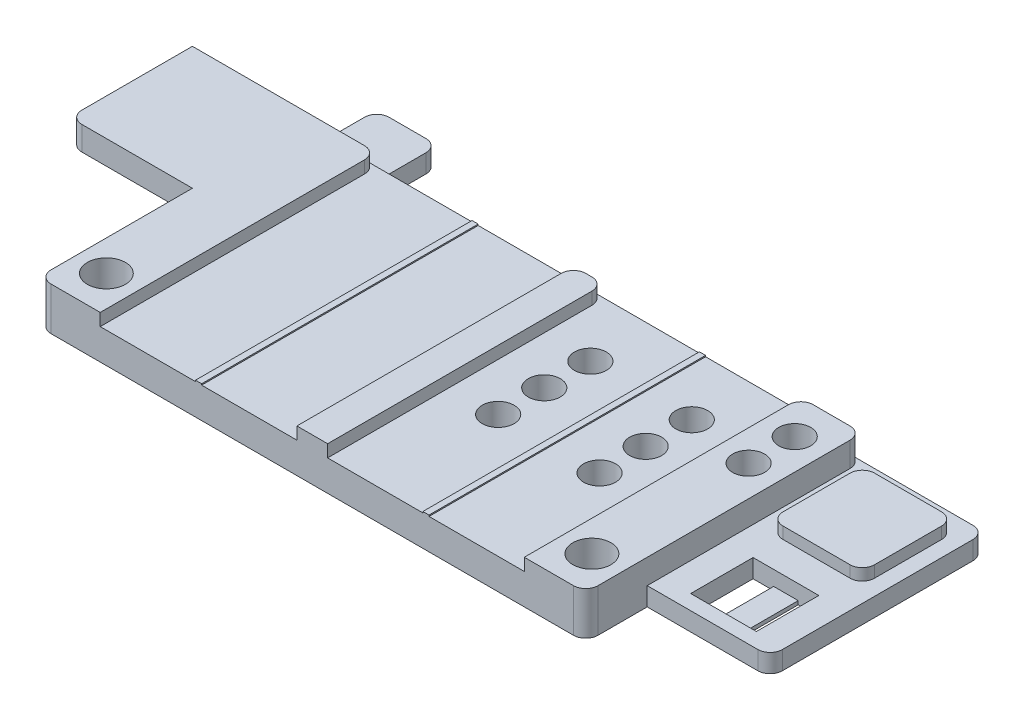
SolidWorks part; units mm, degrees
note: The reader was unsure of these and kept them because the rebuilt part matched: shared geometry of "Sketch1<3>", "Sketch1<4>", "Sketch5<3>", "Sketch5<4>", "Sketch5<5>", "Sketch8<3>".
ref_plane "Front Plane" through (0, 0, 0) normal (0, 0, 1) x (1, 0, 0)
ref_plane "Top Plane" through (0, 0, 0) normal (0, 1, 0) x (1, 0, 0)
ref_plane "Right Plane" through (0, 0, 0) normal (1, 0, 0) x (0, 0, -1)
sketch "Sketch1" plane through (0, 0, 0) normal (0, 1, 0) x (1, 0, 0)
  line L0 (0, 108.5954) -> (0, -94.6715) construction
  line L1 (-125.0313, 0) -> (305.9503, 0) construction
  line L10 (134.5, 0) -> (134.5, 45)
  line L11 (134.5, 45) -> (119, 45)
  line L12 (119, 45) -> (119, 0)
  line L13 (119, 0) -> (134.5, 0)
  line L14 (119, 45) -> (118, 45)
  line L15 (118, 45) -> (118, 0)
  line L16 (118, 0) -> (119, 0)
  line L18 (118, 45) -> (102.5, 45)
  line L22 (100, 108.5954) -> (100, 0) construction
  line L23 (102.5, 45) -> (102.5, 0)
  line L24 (102.5, 0) -> (118, 0)
  line L25 (102.5, 45) -> (97.5, 45)
  line L26 (97.5, 45) -> (97.5, 0)
  line L27 (97.5, 0) -> (102.5, 0)
  line L28 (97.5, 45) -> (82, 45)
  line L29 (82, 45) -> (82, 0)
  line L30 (82, 0) -> (97.5, 0)
  line L31 (82, 45) -> (81, 45)
  line L32 (81, 45) -> (81, 0)
  line L33 (81, 0) -> (82, 0)
  line L34 (81, 45) -> (65.5, 45)
  line L35 (65.5, 45) -> (65.5, 0)
  line L36 (65.5, 0) -> (81, 0)
  line L37 (134.5, 45) -> (144.5, 45)
  line L38 (144.5, 45) -> (144.5, 0)
  line L39 (144.5, 0) -> (134.5, 0)
  line L40 (65.5, 45) -> (55.5, 45)
  line L41 (55.5, 45) -> (55.5, 0)
  line L42 (55.5, 0) -> (65.5, 0)
  circle A10 centre (110.25, 35) radius 2.6
  circle A11 centre (110.25, 27.5) radius 2.6
  circle A12 centre (110.25, 20) radius 2.6
  circle A13 centre (126.75, 35) radius 2.6
  circle A14 centre (126.75, 27.5) radius 2.6
  circle A15 centre (126.75, 20) radius 2.6
  circle A16 centre (139.5, 39) radius 2.6
  circle A17 centre (139.5, 31.5) radius 2.6
  point P7 (100, 45)
  point P38 (110.25, 45)
  point P44 (126.75, 45)
  point P46 (139.5, 45)
  dimension "D6" = 5
  dimension "D7" = 15.5
  dimension "D8" = 1
  dimension "D9" = 15.5
  dimension "D12" = 7.5
  dimension "D14" = 10
  dimension "D10" = 5.2
  dimension "D13" = 7.5
  dimension "D15" = 7.5
  dimension "D16" = 10
  dimension "D2" = 45
  dimension "D3" = 15.5
  dimension "D4" = 1
  dimension "D5" = 15.5
  dimension "D11" = 100
  dimension "D17" = 6
  dimension "D18" = 10
extrude "Boss-Extrude1" add sketch "Sketch1" along normal blind 5 contours L35 L36 L32 L34 | L29 L30 L26 L28 | L23 L24 L15 L18 A12 A11 A10 | L12 L13 L10 L11 A15 A14 A13
extrude "Boss-Extrude2" add sketch "Sketch1<3>" along normal blind 5.2 contours L32 L33 L29 L31 | L15 L16 L12 L14
sketch "Sketch1<3>" plane through (0, 0, 0) normal (0, 1, 0) x (1, 0, 0) same geometry as "Sketch1"
extrude "Boss-Extrude3" add sketch "Sketch1<4>" along normal blind 7 contours L26 L27 L23 L25 | L39 L38 L37 L10 A17 A16 | L41 L42 L35 L40
sketch "Sketch1<4>" plane through (0, 0, 0) normal (0, 1, 0) x (1, 0, 0) same geometry as "Sketch1"
sketch "Sketch2" plane through (0, 0, 0) normal (0, -1, 0) x (-1, 0, 0)
  line L0 (-139.5, 31.5) -> (-139.5, 39) construction
  line L1 (-135.75, 42.75) -> (-143.25, 42.75)
  line L2 (-135.75, 42.75) -> (-135.75, 27.75)
  line L3 (-135.75, 27.75) -> (-143.25, 27.75)
  line L4 (-143.25, 42.75) -> (-143.25, 27.75)
  line L5 (-135.75, 42.75) -> (-143.25, 27.75) construction
  line L6 (-135.75, 27.75) -> (-143.25, 42.75) construction
  point P0 (-139.5, 35.25)
  dimension "D1" = 7.5
  dimension "D2" = 15
extrude "Cut-Extrude1" cut sketch "Sketch2" against normal blind 1.1
sketch "Sketch3" plane through (0, 7, 0) normal (0, 1, 0) x (1, 0, 0)
  line L0 (100, 49.6455) -> (100, -11.2034) construction
  line L2 (55.5, 0) -> (65.5, 0) construction
  line L3 (55.5, 45) -> (55.5, 0) construction
  circle A0 centre (60.5, 6) radius 3.1
  circle A1 centre (139.5, 6) radius 3.1
  point P9 (60.5, 0)
  dimension "D1" = 6.2
  dimension "D2" = 6
  dimension "D3" = 5
  dimension "D4" = 39.5
extrude "Cut-Extrude2" cut sketch "Sketch3" against normal through all
sketch "Sketch5" plane through (0, 0, 0) normal (0, 1, 0) x (1, 0, 0)
  line L0 (144.5, 25) -> (164.5, 25)
  line L1 (144.5, 45) -> (144.5, 0) construction
  line L2 (164.5, 25) -> (164.5, 45)
  line L3 (164.5, 45) -> (144.5, 45)
  line L4 (144.5, 45) -> (144.5, 25)
  line L5 (35.5, 25) -> (55.5, 25)
  line L6 (147.05, 42.45) -> (161.95, 42.45)
  line L7 (147.05, 42.45) -> (147.05, 27.55)
  line L8 (147.05, 27.55) -> (161.95, 27.55)
  line L9 (161.95, 42.45) -> (161.95, 27.55)
  line L10 (147.05, 42.45) -> (161.95, 27.55) construction
  line L11 (147.05, 27.55) -> (161.95, 42.45) construction
  line L12 (55.5, 25) -> (55.5, 45)
  line L13 (55.5, 45) -> (35.5, 45)
  line L14 (35.5, 45) -> (35.5, 25)
  line L15 (37.9, 42.6) -> (53.1, 42.6)
  line L16 (37.9, 42.6) -> (37.9, 27.4)
  line L17 (37.9, 27.4) -> (53.1, 27.4)
  line L18 (53.1, 42.6) -> (53.1, 27.4)
  line L19 (37.9, 42.6) -> (53.1, 27.4) construction
  line L20 (37.9, 27.4) -> (53.1, 42.6) construction
  point P5 (154.5, 35)
  point P13 (154.5, 45)
  point P15 (164.5, 35)
  point P19 (45.5, 35)
  point P25 (45.5, 45)
  point P26 (55.5, 35)
  line M28 (55.5, 0) -> (55.5, 45)
  line M30 (144.5, 45) -> (144.5, 0)
  dimension "D1" = 20
  dimension "D2" = 20
  dimension "D3" = 14.9
  dimension "D4" = 14.9
  dimension "D5" = 20
  dimension "D6" = 20
  dimension "D7" = 15.2
  dimension "D8" = 15.2
extrude "Boss-Extrude4" add sketch "Sketch5" along normal blind 3 contours L3 L2 L0 L9 L6 L7 L8 M30 | L6 L9 L8 L7
extrude "Boss-Extrude5" add sketch "Sketch5<3>" along normal blind 4.9 contours L6 L9 L8 L7
sketch "Sketch5<3>" plane through (0, 0, 0) normal (0, 1, 0) x (1, 0, 0) same geometry as "Sketch5"
extrude "Boss-Extrude6" add sketch "Sketch5<4>" against normal blind 3.9 from surface at 7 contours L14 L13 L5 L18 L15 L16 L17 M28 starting at face at (60.5, 7, -2.9)
sketch "Sketch5<4>" plane through (0, 0, 0) normal (0, 1, 0) x (1, 0, 0) same geometry as "Sketch5"
extrude "Boss-Extrude7" add sketch "Sketch5<5>" against normal blind 1 from surface at 7 contours L15 L18 L17 L16 starting at face at (60.5, 7, -2.9)
sketch "Sketch5<5>" plane through (0, 0, 0) normal (0, 1, 0) x (1, 0, 0) same geometry as "Sketch5"
fillet "Fillet1" radius 2 4 edges at (147.05, 3.95, -27.55) (147.05, 3.95, -42.45) (161.95, 3.95, -42.45) (161.95, 3.95, -27.55)
sketch "Sketch6" plane through (0, 7, 0) normal (0, 1, 0) x (1, 0, 0)
  line L0 (65.5, 45) -> (65.5, 55)
  line L1 (65.5, 55) -> (55.5, 55)
  line L2 (55.5, 55) -> (55.5, 45)
  line L3 (65.5, 45) -> (35.5, 45) construction
  line L4 (55.5, 45) -> (65.5, 45)
  dimension "D1" = 10
  dimension "D2" = 10
extrude "Boss-Extrude8" add sketch "Sketch6" along normal blind 3 from surface at -7 starting at face at (60.5, 0, -2.9)
chamfer "Chamfer1" distance 1 angle 45 1 edges at (45.5, 3.1, -45)
sketch "Sketch8" plane through (0, 0, 0) normal (0, 1, 0) x (1, 0, 0)
  line L0 (-3.6838, 0) -> (193.3605, 0) construction
  line L1 (164.5, 25) -> (164.5, 10)
  line L2 (164.5, 10) -> (144.5, 10)
  line L3 (144.5, 45) -> (144.5, 0) construction
  line L4 (144.5, 10) -> (144.5, 25)
  line L5 (144.5, 25) -> (164.5, 25)
  line L6 (154.5, 25) -> (154.5, 10) construction
  line L7 (152.5, 22.575) -> (152.5, 12.425)
  line L8 (149.15, 12.425) -> (159.85, 12.425)
  line L9 (149.15, 12.425) -> (149.15, 22.575)
  line L10 (149.15, 22.575) -> (159.85, 22.575)
  line L11 (159.85, 12.425) -> (159.85, 22.575)
  line L12 (149.15, 12.425) -> (159.85, 22.575) construction
  line L13 (149.15, 22.575) -> (159.85, 12.425) construction
  line L14 (156.5, 22.575) -> (156.5, 12.425)
  point P13 (154.5, 17.5)
  dimension "D1" = 10.7
  dimension "D2" = 10.15
  dimension "D3" = 15
  dimension "D4" = 2
extrude "Boss-Extrude9" add sketch "Sketch8" along normal blind 3 contours L5 L4 L2 L1 L11 L8 L9 L10
extrude "Boss-Extrude10" add sketch "Sketch8<3>" along normal blind 0.6 contours L14 L10 L7 L8
sketch "Sketch8<3>" plane through (0, 0, 0) normal (0, 1, 0) x (1, 0, 0) same geometry as "Sketch8"
fillet "Fillet3" radius 2 12 edges at (35.5, 5.05, -25) (144.5, 3.5, 0) (55.5, 3.5, 0) (65.5, 1.5, -55) (65.5, 6, -45) (134.5, 6, -45) (144.5, 5, -45) (97.5, 6, -45) (102.5, 6, -45) (55.5, 1.5, -55) (164.5, 1.5, -45) (164.5, 1.5, -10)
